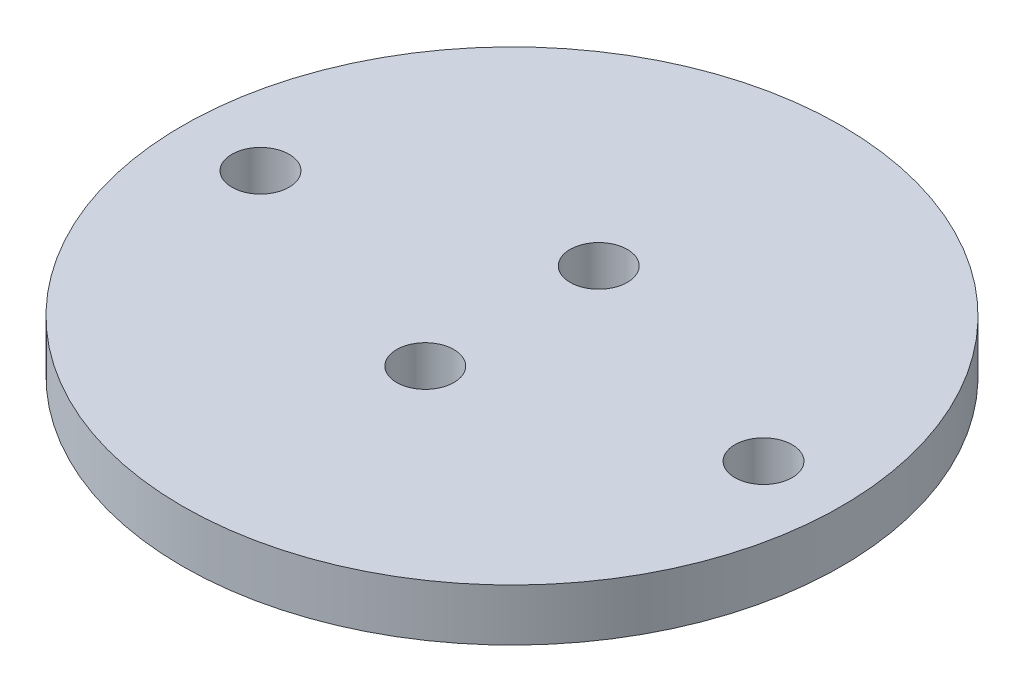
SolidWorks part; units mm, degrees
material "Pine"
ref_plane "Front Plane" through (0, 0, 0) normal (0, 0, 1) x (1, 0, 0)
ref_plane "Top Plane" through (0, 0, 0) normal (0, 1, 0) x (1, 0, 0)
ref_plane "Right Plane" through (0, 0, 0) normal (1, 0, 0) x (0, 0, -1)
sketch "Sketch1" plane through (0, 0, 0) normal (0, 1, 0) x (1, 0, 0)
  line L0 (14.5, 0) -> (-14.5, 0) construction
  line L1 (0, 5) -> (0, -5) construction
  circle A0 centre (0, 0) radius 19
  circle A1 centre (-14.5, 0) radius 1.65
  circle A2 centre (14.5, 0) radius 1.65
  circle A3 centre (0, 5) radius 1.65
  circle A4 centre (0, -5) radius 1.65
  point P7 (0, 0)
  point P12 (0, 0)
  dimension "D1" = 38
  dimension "D2" = 3.3
  dimension "D3" = 29
  dimension "D4" = 10
extrude "Boss-Extrude1" add sketch "Sketch1" along normal blind 3
